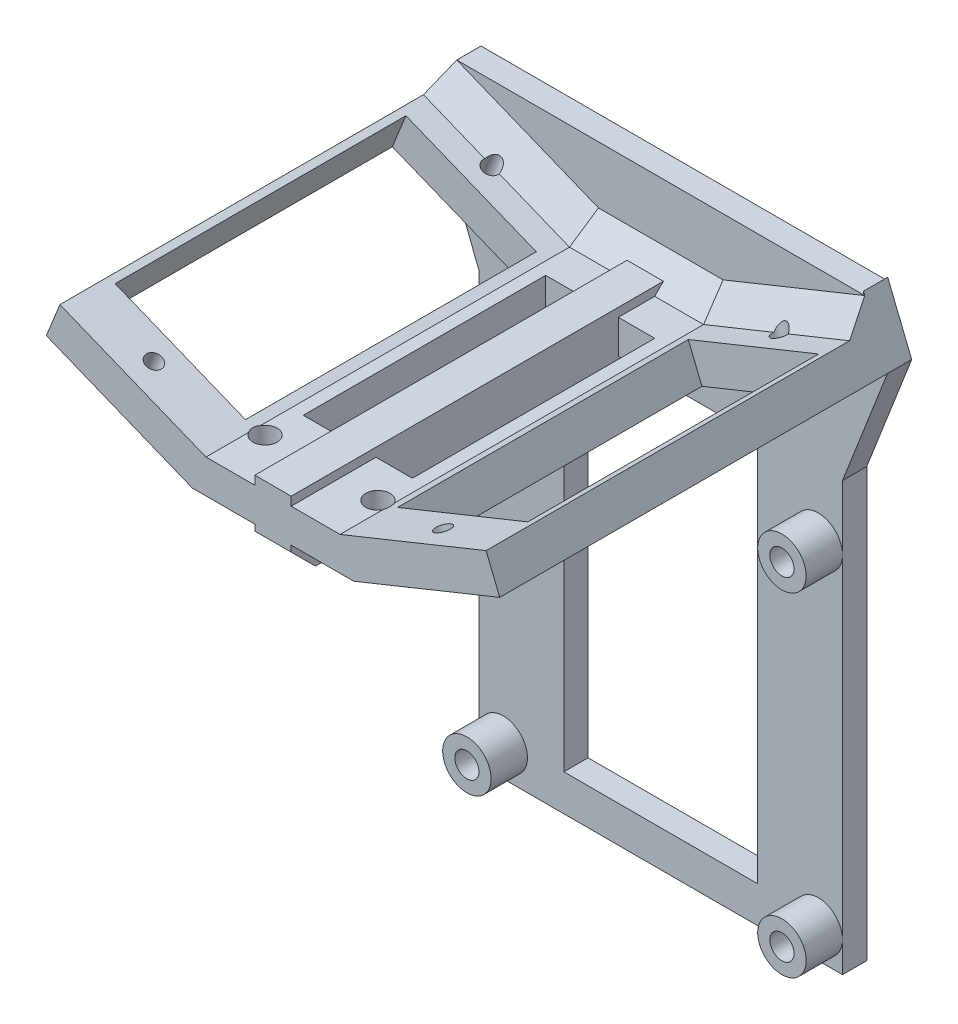
SolidWorks part; units mm, degrees
ref_plane "前基準面" through (0, 0, 0) normal (0, 0, 1) x (1, 0, 0)
ref_plane "上基準面" through (0, 0, 0) normal (0, 1, 0) x (1, 0, 0)
ref_plane "右基準面" through (0, 0, 0) normal (1, 0, 0) x (0, 0, -1)
sketch "草圖1" plane through (0, 0, 0) normal (0, 0, 1) x (1, 0, 0)
  line L0 (-15, 0) -> (15, 0)
  line L1 (-15, 0) -> (-15, -1)
  line L2 (18.7087, -10.1794) -> (15, -11.6779)
  line L3 (15, -11.6779) -> (15, -55)
  line L4 (15, -55) -> (-15, -55)
  line L5 (-15, -55) -> (-15, -11.6779)
  line L6 (-15, -11.6779) -> (-18.7087, -10.1794)
  line L7 (-15, -1) -> (-18.7087, -10.1794)
  line L8 (0, 15.1551) -> (0, -26.7536) construction
  line L9 (15, 0) -> (15, -1)
  line L10 (15, -1) -> (18.7087, -10.1794)
  dimension "D7" = 68
  dimension "D8" = 4
  dimension "D9" = 1
  dimension "D10" = 1
  dimension "D1" = 30
  dimension "D2" = 15
  dimension "D3" = 30
  dimension "D4" = 15
  dimension "D5" = 55
  dimension "D6" = 136
  dimension "D11" = 90
extrude "填料-伸長1" add sketch "草圖1" along normal blind 2
sketch "草圖2" plane through (0, 0, 2) normal (0, 0, 1) x (1, 0, 0)
  line L0 (0, 35.4377) -> (0, -39.094) construction
  line L2 (-18.7087, -10.1794) -> (-6.6553, -15.0493)
  line L3 (-6.6553, -15.0493) -> (6.6553, -15.0493)
  line L4 (6.6553, -15.0493) -> (18.7087, -10.1794)
  line L5 (15, -11.6779) -> (18.7087, -10.1794) construction
  line L6 (-18.7087, -10.1794) -> (-15, -11.6779) construction
  line L7 (-18.7087, -10.1794) -> (-17.5849, -7.3979)
  line L8 (-15, -1) -> (-18.7087, -10.1794) construction
  line L9 (-17.5849, -7.3979) -> (-5.5315, -12.2678)
  line L10 (-5.5315, -12.2678) -> (5.5315, -12.2678)
  line L11 (5.5315, -12.2678) -> (17.5849, -7.3979)
  line L12 (18.7087, -10.1794) -> (15, -1) construction
  line L13 (17.5849, -7.3979) -> (18.7087, -10.1794)
  dimension "D1" = 13
  dimension "D2" = 3
  dimension "D3" = 3
  dimension "D4" = 13
  dimension "D5" = 13
extrude "填料-伸長2" add sketch "草圖2" along normal blind 32 and the other way blind 2
sketch "草圖3" plane through (4.9147, -15.7526, 0) normal (-0.3746, 0.9272, 0) x (0.9272, 0.3746, 0)
  line L1 (14.8774, -34) -> (1.8774, -34) construction
  line L2 (14.8774, -2) -> (14.8774, -34) construction
  line L5 (14.8774, -6) -> (2.6774, -6)
  line L6 (14.8774, -6) -> (14.8774, -30)
  line L7 (14.8774, -30) -> (2.6774, -30)
  line L8 (2.6774, -6) -> (2.6774, -30)
  circle A2 centre (8.7774, -4.1) radius 0.65
  circle A3 centre (8.7774, -31.9) radius 0.65
  dimension "D7" = 1.3
  dimension "D2" = 24
  dimension "D3" = 12.2
  dimension "D4" = 27.8
  dimension "D5" = 1.9
  dimension "D6" = 4
  dimension "D11" = 6.1
extrude "除料-伸長5" cut sketch "草圖3" along normal up to next
sketch "草圖12" plane through (-6.161, -15.249, 0) normal (-0.3746, -0.9272, 0) x (0.9272, -0.3746, 0)
  line L0 (-13.5332, 34) -> (-13.5332, 0) construction
  line L1 (-13.5332, 30) -> (-1.3332, 30)
  line L2 (-13.5332, 30) -> (-13.5332, 6)
  line L3 (-13.5332, 6) -> (-1.3332, 6)
  line L4 (-1.3332, 30) -> (-1.3332, 6)
  line L5 (-13.5332, 34) -> (-0.5332, 34) construction
  circle A0 centre (-7.4332, 31.9) radius 0.65
  circle A1 centre (-7.4332, 4.1) radius 0.65
  dimension "D7" = 1.3
  dimension "D8" = 1.3
  dimension "D1" = 12.2
  dimension "D2" = 24
  dimension "D3" = 4
  dimension "D4" = 27.8
  dimension "D5" = 1.9
  dimension "D6" = 6.1
extrude "除料-伸長7" cut sketch "草圖12" against normal up to next
sketch "草圖13" plane through (0, 0, 2) normal (0, 0, 1) x (1, 0, 0)
  line L1 (-15, -55) -> (15, -55) construction
  line L2 (-6.6553, -15.0493) -> (6.6553, -15.0493) construction
  line L3 (-8, -20.0493) -> (8, -20.0493)
  line L4 (-8, -20.0493) -> (-8, -52)
  line L5 (-8, -52) -> (8, -52)
  line L6 (8, -20.0493) -> (8, -52)
  line L7 (-8, -20.0493) -> (8, -52) construction
  line L8 (-8, -52) -> (8, -20.0493) construction
  circle A0 centre (-13, -25) radius 1
  circle A1 centre (13, -25) radius 1
  circle A2 centre (-13, -52.5) radius 1
  circle A3 centre (13, -52.5) radius 1
  point P11 (0, -36.0247)
  dimension "D4" = 2
  dimension "D5" = 2
  dimension "D6" = 2
  dimension "D7" = 2
  dimension "D1" = 26
  dimension "D2" = 27.5
  dimension "D3" = 2.5
  dimension "D8" = 13
  dimension "D9" = 16
  dimension "D10" = 3
  dimension "D11" = 5
extrude "除料-伸長8" cut sketch "草圖13" against normal up to next
chamfer "導角4" distance 1 angle 45 2 edges at (-15, 0, 1) (15, 0, 1)
chamfer "導角5" distance 2 angle 45 3 edges at (11.5582, -9.8328, 2) (0, -12.2678, 2) (-11.5582, -9.8328, 2)
sketch "草圖14" plane through (0, 0, 34) normal (0, 0, 1) x (1, 0, 0)
  line L1 (-1.5, -17.5493) -> (1.5, -17.5493)
  line L2 (-1.5, -17.5493) -> (-1.5, -11.5493)
  line L3 (-1.5, -11.5493) -> (1.5, -11.5493)
  line L4 (1.5, -17.5493) -> (1.5, -11.5493)
  line L5 (-1.5, -17.5493) -> (1.5, -11.5493) construction
  line L6 (-1.5, -11.5493) -> (1.5, -17.5493) construction
  line L7 (6.6553, -15.0493) -> (-6.6553, -15.0493) construction
  point P0 (0, -14.5493)
  dimension "D1" = 6
  dimension "D2" = 3
  dimension "D3" = 2.5
extrude "填料-伸長8" add sketch "草圖14" against normal up to surface (32 mm away) up to face at (0, -36.0247, 2)
chamfer "導角6" distance 2 angle 45 1 edges at (0, -17.5493, 34)
sketch "草圖15" plane through (0, 0, 2) normal (0, 0, 1) x (1, 0, 0)
  circle A0 centre (-13, -25) radius 1
  circle A1 centre (-13, -25) radius 2
  circle A2 centre (13, -25) radius 1
  circle A3 centre (13, -25) radius 2
  circle A4 centre (13, -52.5) radius 1
  circle A5 centre (13, -52.5) radius 2
  circle A6 centre (-13, -52.5) radius 1
  circle A7 centre (-13, -52.5) radius 2
extrude "填料-伸長9" add sketch "草圖15" along normal blind 3
sketch "草圖16" plane through (0, -15.0493, 0) normal (0, -1, 0) x (1, 0, 0)
  line L0 (-1.5, 2) -> (-1.5, 32) construction
  line L1 (-1.5, 27) -> (-4.5, 27)
  line L2 (-1.5, 27) -> (-1.5, 7)
  line L3 (-1.5, 7) -> (-4.5, 7)
  line L4 (-4.5, 27) -> (-4.5, 7)
  line L5 (1.5, 2) -> (1.5, 34) construction
  line L6 (1.5, 27) -> (4.5, 27)
  line L7 (1.5, 27) -> (1.5, 7)
  line L8 (1.5, 7) -> (4.5, 7)
  line L9 (4.5, 27) -> (4.5, 7)
  dimension "D1" = 3
  dimension "D2" = 3
  dimension "D3" = 20
  dimension "D4" = 20
  dimension "D5" = 7
  dimension "D6" = 7
extrude "除料-伸長9" cut sketch "草圖16" against normal up to next
sketch "草圖17" plane through (0, 0, 0) normal (0, 0, -1) x (-1, 0, 0)
  line L0 (-18.7087, -10.1794) -> (-15, -19.6779)
  line L1 (-15, -55) -> (-15, -11.6779) construction
  line L2 (-15, -19.6779) -> (-15, -11.6779)
  line L3 (-15, -11.6779) -> (-18.7087, -10.1794)
  line L4 (18.7087, -10.1794) -> (15, -11.6779)
  line L5 (15, -11.6779) -> (15, -19.6779)
  line L6 (15, -11.6779) -> (15, -55) construction
  line L7 (15, -19.6779) -> (18.7087, -10.1794)
  dimension "D1" = 8
extrude "填料-伸長10" add sketch "草圖17" against normal up to surface (2 mm away) up to face at (0, -36.0247, 2)
sketch "草圖18" plane through (0, 0, 34) normal (0, 0, 1) x (1, 0, 0)
  line L0 (-17.5849, -7.3979) -> (-18.7087, -10.1794)
  line L1 (-18.7087, -10.1794) -> (-18.1524, -10.4042)
  line L2 (-18.7087, -10.1794) -> (-6.6553, -15.0493) construction
  line L3 (-18.1524, -10.4042) -> (-17.0286, -7.6227)
  line L4 (-12.5246, -9.4424) -> (-17.5849, -7.3979) construction
  line L5 (-17.0286, -7.6227) -> (-17.5849, -7.3979)
  line L7 (17.5849, -7.3979) -> (18.7087, -10.1794)
  line L8 (18.7087, -10.1794) -> (18.1524, -10.4042)
  line L9 (6.6553, -15.0493) -> (18.7087, -10.1794) construction
  line L10 (18.1524, -10.4042) -> (17.0286, -7.6227)
  line L11 (17.5849, -7.3979) -> (12.5246, -9.4424) construction
  line L12 (17.0286, -7.6227) -> (17.5849, -7.3979)
  dimension "D1" = 0.6
  dimension "D2" = 0.6
extrude "填料-伸長11" add sketch "草圖18" against normal up to surface (28 mm away) up to face at (-12.491, -11.0738, 6)
sketch "草圖19" plane through (0, -17.5493, 0) normal (0, -1, 0) x (1, 0, 0)
  line L0 (-6.6553, 2) -> (-6.6553, 34) construction
  line L3 (6.6553, 2) -> (6.6553, 34) construction
  circle A1 centre (-4.6553, 30) radius 1
  circle A2 centre (4.6553, 30) radius 1
  dimension "D1" = 2
  dimension "D2" = 30
  dimension "D3" = 2
  dimension "D4" = 2
  dimension "D5" = 2
extrude "除料-伸長10" cut sketch "草圖19" against normal up to next
sketch "草圖20" plane through (0, 0, 2) normal (0, 0, 1) x (1, 0, 0)
  line L1 (-16.8357, -5.5435) -> (16.7306, -5.5435)
  line L2 (-16.8357, -5.5435) -> (-16.8357, 1.144)
  line L3 (-16.8357, 1.144) -> (16.7306, 1.144)
  line L4 (16.7306, -5.5435) -> (16.7306, 1.144)
extrude "除料-伸長11" cut sketch "草圖20" against normal up to next
